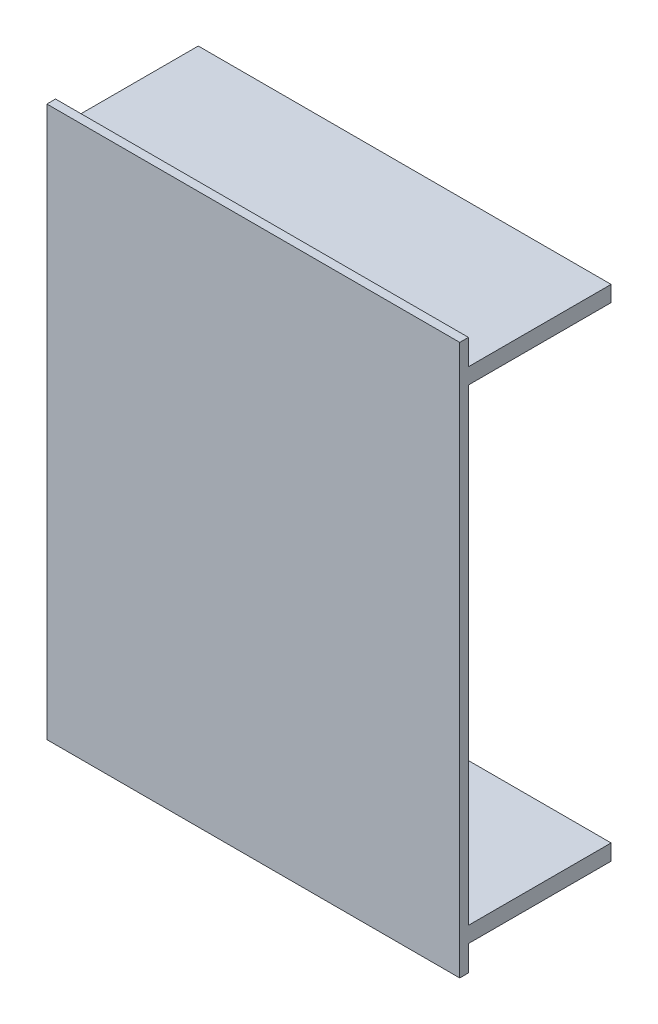
SolidWorks part; units mm, degrees
ref_plane "Front Plane" through (0, 0, 0) normal (0, 0, 1) x (1, 0, 0)
ref_plane "Top Plane" through (0, 0, 0) normal (0, 1, 0) x (1, 0, 0)
ref_plane "Right Plane" through (0, 0, 0) normal (1, 0, 0) x (0, 0, -1)
sketch "Sketch1" plane through (0, 0, 0) normal (0, 0, 1) x (1, 0, 0)
  line L1 (0, 0) -> (300, 0)
  line L2 (0, 0) -> (0, 400)
  line L3 (0, 400) -> (300, 400)
  line L4 (300, 0) -> (300, 400)
  dimension "D1" = 300
  dimension "D2" = 400
extrude "Boss-Extrude1" add sketch "Sketch1" along normal blind 6.3
sketch "Sketch4" plane through (0, 0, 0) normal (1, 0, 0) x (0, 0, -1)
  line L0 (0, 0) -> (0, 400) construction
  line L1 (0, 18.5) -> (103.7, 18.5)
  line L2 (0, 18.5) -> (0, 30)
  line L3 (0, 30) -> (103.7, 30)
  line L4 (103.7, 18.5) -> (103.7, 30)
  line L5 (-6.3, 200) -> (0, 200) construction
  line L6 (-6.3, 0) -> (-6.3, 400) construction
  line L7 (0, 370) -> (103.7, 370)
  line L8 (103.7, 381.5) -> (103.7, 370)
  line L9 (0, 381.5) -> (103.7, 381.5)
  line L10 (0, 381.5) -> (0, 370)
  dimension "D1" = 11.5
  dimension "D2" = 110
  dimension "D3" = 340
extrude "Boss-Extrude2" add sketch "Sketch4" along normal up to surface (300 mm away) up to face at (300, 200, 3.15)
ref_plane "Plane1" through (0, 0, -103.7) normal (0, 0, -1) x (-1, 0, 0)
